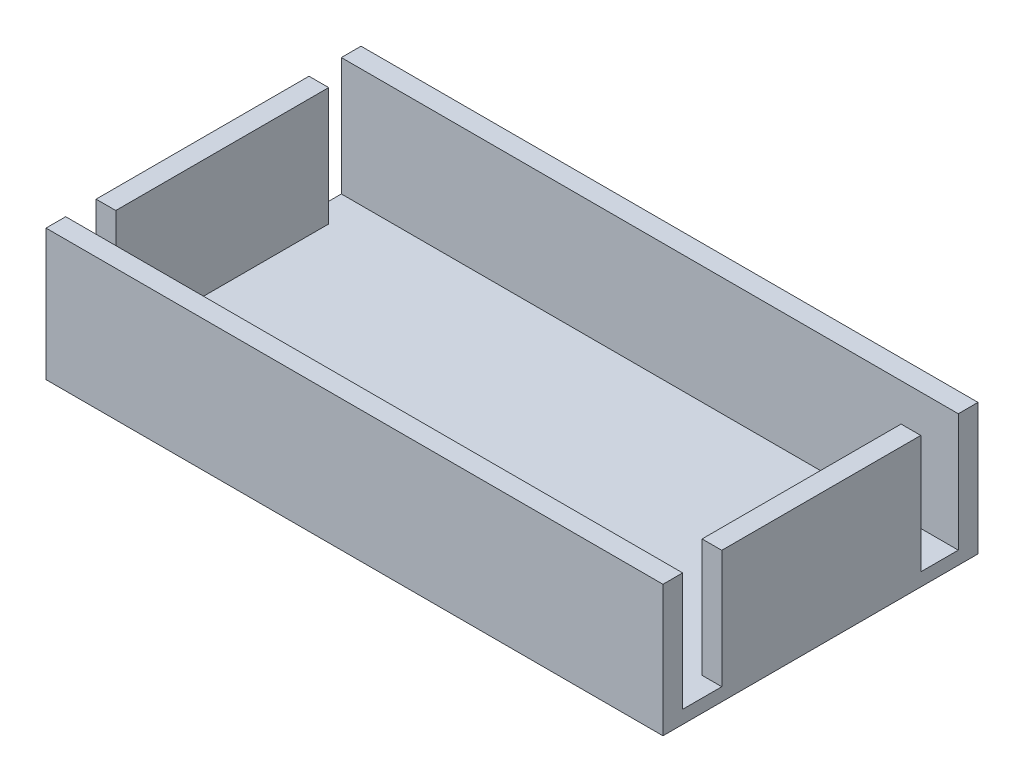
SolidWorks part; units mm, degrees
note: The reader was unsure of these and kept them because the rebuilt part matched: shared geometry of "Sketch1<3>".
ref_plane "Front Plane" through (0, 0, 0) normal (0, 0, 1) x (1, 0, 0)
ref_plane "Top Plane" through (0, 0, 0) normal (0, 1, 0) x (1, 0, 0)
ref_plane "Right Plane" through (0, 0, 0) normal (1, 0, 0) x (0, 0, -1)
sketch "Sketch1" plane through (0, 0, 0) normal (0, 1, 0) x (1, 0, 0)
  line L0 (-23.5, 12) -> (23.5, 12)
  line L1 (-22, 10.5) -> (22, 10.5)
  line L2 (-22, 10.5) -> (-22, -10.5)
  line L3 (-22, -10.5) -> (22, -10.5)
  line L4 (22, 10.5) -> (22, -10.5)
  line L5 (-22, 10.5) -> (22, -10.5) construction
  line L6 (-22, -10.5) -> (22, 10.5) construction
  line L7 (23.5, 12) -> (23.5, -12)
  line L8 (-23.5, -12) -> (23.5, -12)
  line L9 (-23.5, 12) -> (-23.5, -12)
  point P0 (0, 0)
  dimension "D1" = 44
  dimension "D2" = 21
  dimension "D3" = 1.5
extrude "Boss-Extrude1" add sketch "Sketch1" along normal blind 1 contours L0 L9 L8 L7 L1 L4 L3 L2 | L4 L1 L2 L3
extrude "Boss-Extrude2" add sketch "Sketch1<3>" along normal blind 10 contours L8 L7 L0 L9
sketch "Sketch1<3>" plane through (0, 0, 0) normal (0, 1, 0) x (1, 0, 0) same geometry as "Sketch1"
sketch "Sketch2" plane through (0, 10, 0) normal (0, 1, 0) x (1, 0, 0)
  line L0 (23.5, -12) -> (23.5, 12) construction
  line L1 (22, 10.5) -> (23.5, 10.5)
  line L2 (22, 10.5) -> (22, 7.639)
  line L3 (22, 7.639) -> (23.5, 7.639)
  line L4 (23.5, 10.5) -> (23.5, 7.639)
  line L5 (-23.5, 12) -> (-23.5, -12) construction
  line L6 (22, -10.5) -> (23.5, -10.5)
  line L7 (22, -10.5) -> (22, -7.5194)
  line L8 (22, -7.5194) -> (23.5, -7.5194)
  line L9 (23.5, -10.5) -> (23.5, -7.5194)
  line L10 (-22, 10.5) -> (-23.5, 10.5)
  line L11 (-22, 10.5) -> (-22, 8.0362)
  line L12 (-22, 8.0362) -> (-23.5, 8.0362)
  line L13 (-23.5, 10.5) -> (-23.5, 8.0362)
  line L15 (-22, -10.5) -> (-23.5, -10.5)
  line L16 (-22, -10.5) -> (-22, -8.1848)
  line L17 (-22, -8.1848) -> (-23.5, -8.1848)
  line L18 (-23.5, -10.5) -> (-23.5, -8.1848)
extrude "Cut-Extrude1" cut sketch "Sketch2" against normal blind 9
